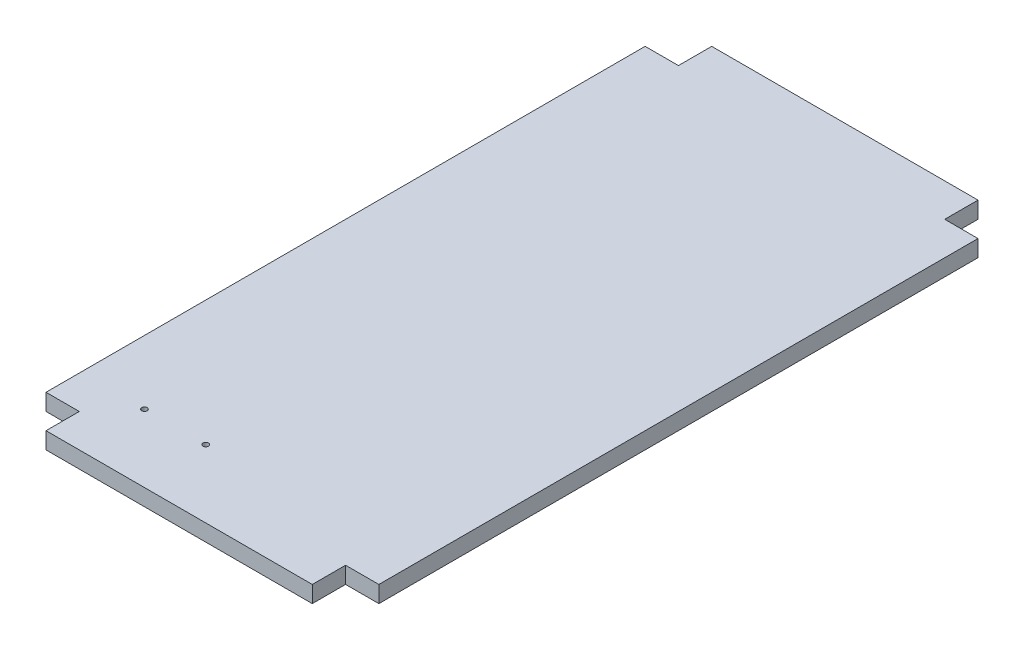
SolidWorks part; units mm, degrees
material "Oak"
ref_plane "Front Plane" through (0, 0, 0) normal (0, 0, 1) x (1, 0, 0)
ref_plane "Top Plane" through (0, 0, 0) normal (0, 1, 0) x (1, 0, 0)
ref_plane "Right Plane" through (0, 0, 0) normal (1, 0, 0) x (0, 0, -1)
sketch "Sketch1" plane through (0, 0, 0) normal (0, 1, 0) x (1, 0, 0)
  line L0 (-194.7505, -920.1839) -> (-194.7505, -234.3839)
  line L1 (-194.7505, -234.3839) -> (-156.6505, -234.3839)
  line L2 (-156.6505, -234.3839) -> (-156.6505, -196.2839)
  line L3 (-156.6505, -196.2839) -> (148.1495, -196.2839)
  line L4 (148.1495, -196.2839) -> (148.1495, -234.3839)
  line L5 (148.1495, -234.3839) -> (186.2495, -234.3839)
  line L6 (186.2495, -234.3839) -> (186.2495, -920.1839)
  line L7 (186.2495, -920.1839) -> (148.1495, -920.1839)
  line L8 (148.1495, -920.1839) -> (148.1495, -958.2839)
  line L9 (148.1495, -958.2839) -> (-156.6505, -958.2839)
  line L10 (-156.6505, -958.2839) -> (-156.6505, -920.1839)
  line L11 (-156.6505, -920.1839) -> (-194.7505, -920.1839)
  line L12 (-121.6375, -880.6539) -> (-194.7505, -880.6539) construction
  line L13 (-121.6375, -880.6539) -> (-121.6375, -958.2839) construction
  line L14 (-121.6375, -880.6539) -> (-51.4375, -880.6539) construction
  circle A0 centre (-121.6375, -880.6539) radius 3.175
  circle A1 centre (-51.4375, -880.6539) radius 3.175
  dimension "D1" = 762
  dimension "D2" = 304.8
  dimension "D3" = 304.8
  dimension "D4" = 38.1
  dimension "D5" = 38.1
  dimension "D6" = 38.1
  dimension "D7" = 685.8
  dimension "D8" = 38.1
  dimension "D9" = 685.8
  dimension "D10" = 38.1
extrude "Boss-Extrude1" add sketch "Sketch1" along normal blind 19.05
